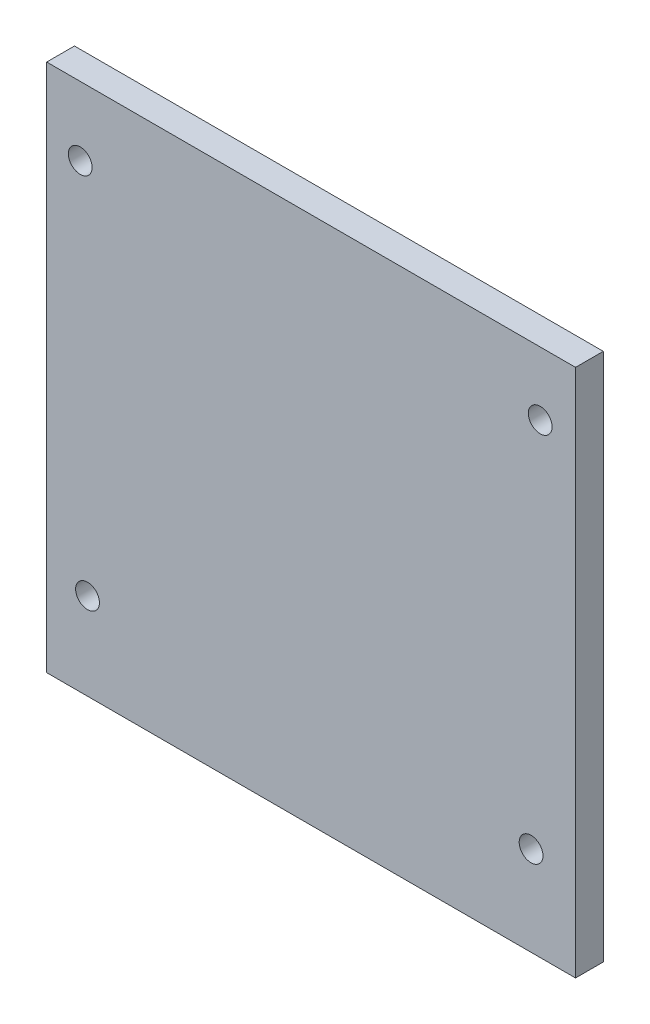
SolidWorks part; units mm, degrees
ref_plane "Front Plane" through (0, 0, 0) normal (0, 0, 1) x (1, 0, 0)
ref_plane "Top Plane" through (0, 0, 0) normal (0, 1, 0) x (1, 0, 0)
ref_plane "Right Plane" through (0, 0, 0) normal (1, 0, 0) x (0, 0, -1)
sketch "Sketch1" plane through (0, 0, 0) normal (0, 0, 1) x (1, 0, 0)
  line L1 (-50.8, -50.8) -> (50.8, -50.8)
  line L2 (-50.8, -50.8) -> (-50.8, 50.8)
  line L3 (-50.8, 50.8) -> (50.8, 50.8)
  line L4 (50.8, -50.8) -> (50.8, 50.8)
  line L5 (-50.8, -50.8) -> (50.8, 50.8) construction
  line L6 (-50.8, 50.8) -> (50.8, -50.8) construction
  point P0 (0, 0)
  dimension "D1" = 101.6
  dimension "D2" = 101.6
extrude "Boss-Extrude1" add sketch "Sketch1" along normal blind 5.334
sketch "Sketch2" plane through (0, 0, 0) normal (0, 0, -1) x (-1, 0, 0)
  circle A0 centre (-42.2593, -33.6151) radius 2.286 construction
  circle A1 centre (-42.2593, -33.6151) radius 2.286
  circle A2 centre (42.9594, -34.103) radius 2.286 construction
  circle A3 centre (42.9594, -34.103) radius 2.286
  circle A4 centre (44.3532, 37.6137) radius 2.286 construction
  circle A5 centre (-44.009, 38.6365) radius 2.286 construction
  circle A6 centre (44.3532, 37.6137) radius 2.286
  circle A7 centre (-44.009, 38.6365) radius 2.286
extrude "Cut-Extrude1" cut sketch "Sketch2" against normal through all
equation "\"D1@Boss-Extrude1\" = \"material\""
equation "\"material\"=\"GMaterial@Platform.assembly\""
